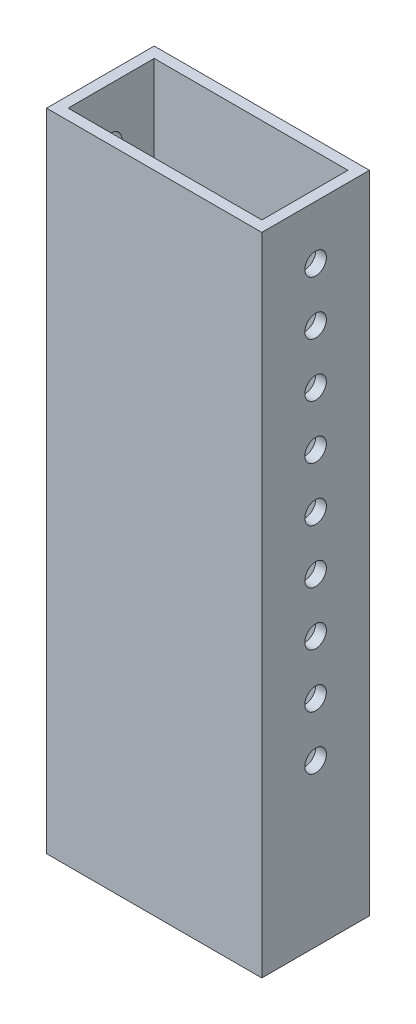
SolidWorks part; units mm, degrees
ref_plane "Front Plane" through (0, 0, 0) normal (0, 0, 1) x (1, 0, 0)
ref_plane "Top Plane" through (0, 0, 0) normal (0, 1, 0) x (1, 0, 0)
ref_plane "Right Plane" through (0, 0, 0) normal (1, 0, 0) x (0, 0, -1)
sketch "Sketch1" plane through (0, 0, 0) normal (0, 1, 0) x (1, 0, 0)
  line L1 (-59.9507, 17.7211) -> (-9.1507, 17.7211)
  line L2 (-59.9507, 17.7211) -> (-59.9507, -7.6789)
  line L3 (-59.9507, -7.6789) -> (-9.1507, -7.6789)
  line L4 (-9.1507, 17.7211) -> (-9.1507, -7.6789)
  line L5 (-59.9507, 17.7211) -> (-9.1507, -7.6789) construction
  line L6 (-59.9507, -7.6789) -> (-9.1507, 17.7211) construction
  line L7 (-57.4107, 15.1811) -> (-11.6907, 15.1811)
  line L8 (-57.4107, 15.1811) -> (-57.4107, -5.1389)
  line L9 (-57.4107, -5.1389) -> (-11.6907, -5.1389)
  line L10 (-11.6907, 15.1811) -> (-11.6907, -5.1389)
  line L11 (-57.4107, 15.1811) -> (-11.6907, -5.1389) construction
  line L12 (-57.4107, -5.1389) -> (-11.6907, 15.1811) construction
  point P0 (-34.5507, 5.0211)
  point P5 (-34.5507, 5.0211)
  dimension "D1" = 25.4
  dimension "D2" = 50.8
  dimension "D3" = 2.54
  dimension "D4" = 2.54
  dimension "D5" = 2.54
  dimension "D6" = 2.54
extrude "Boss-Extrude2" add sketch "Sketch1" along normal blind 152.4
sketch "Sketch2" plane through (-9.1507, 0, 0) normal (1, 0, 0) x (0, 0, -1)
  line L0 (-7.6789, 152.4) -> (17.7211, 152.4) construction
  line L1 (17.7211, 152.4) -> (17.7211, 0) construction
  circle A0 centre (5.0211, 139.7) radius 2.54
  circle A1 centre (5.0211, 127) radius 2.54
  circle A2 centre (5.0211, 114.3) radius 2.54
  circle A3 centre (5.0211, 101.6) radius 2.54
  circle A4 centre (5.0211, 88.9) radius 2.54
  circle A5 centre (5.0211, 76.2) radius 2.54
  circle A6 centre (5.0211, 63.5) radius 2.54
  circle A7 centre (5.0211, 50.8) radius 2.54
  circle A8 centre (5.0211, 38.1) radius 2.54
  dimension "D1" = 5.08
  dimension "D2" = 12.7
  dimension "D3" = 12.7
  dimension "D4" = 9
extrude "Cut-Extrude1" cut sketch "Sketch2" against normal blind 127
